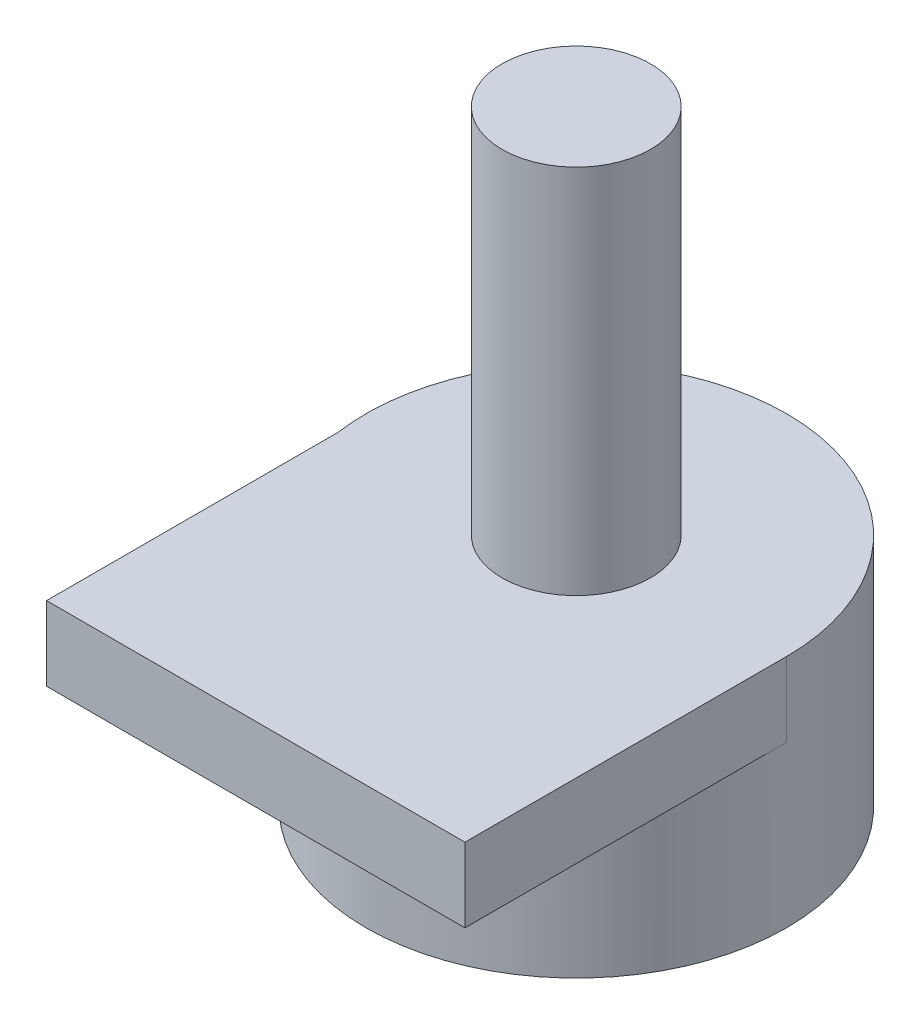
SolidWorks part; units mm, degrees
ref_plane "Front Plane" through (0, 0, 0) normal (0, 0, 1) x (1, 0, 0)
ref_plane "Top Plane" through (0, 0, 0) normal (0, 1, 0) x (1, 0, 0)
ref_plane "Right Plane" through (0, 0, 0) normal (1, 0, 0) x (0, 0, -1)
sketch "Sketch1" plane through (0, 0, 0) normal (0, 1, 0) x (1, 0, 0)
  circle A0 centre (0, 0) radius 8.5
  dimension "D1" = 17
extrude "Boss-Extrude1" add sketch "Sketch1" along normal blind 9.5
sketch "Sketch2" plane through (0, 9.5, 0) normal (0, 1, 0) x (1, 0, 0)
  circle A0 centre (0, 0) radius 3
  dimension "D1" = 6
extrude "Boss-Extrude2" add sketch "Sketch2" along normal blind 15
sketch "Sketch3" plane through (0, 9.5, 0) normal (0, 1, 0) x (1, 0, 0)
  line L0 (-8.4125, 0) -> (8.5, 0)
  line L1 (-8.4125, 0) -> (-8.4125, -13)
  line L2 (8.5, 0) -> (8.5, -13)
  line L3 (-8.4125, -13) -> (8.5, -13)
  line L4 (-9.35, 0) -> (9.35, 0) construction
  circle A0 centre (0, 0) radius 8.5 construction
  dimension "D1" = 13
extrude "Boss-Extrude3" add sketch "Sketch3" against normal blind 3
